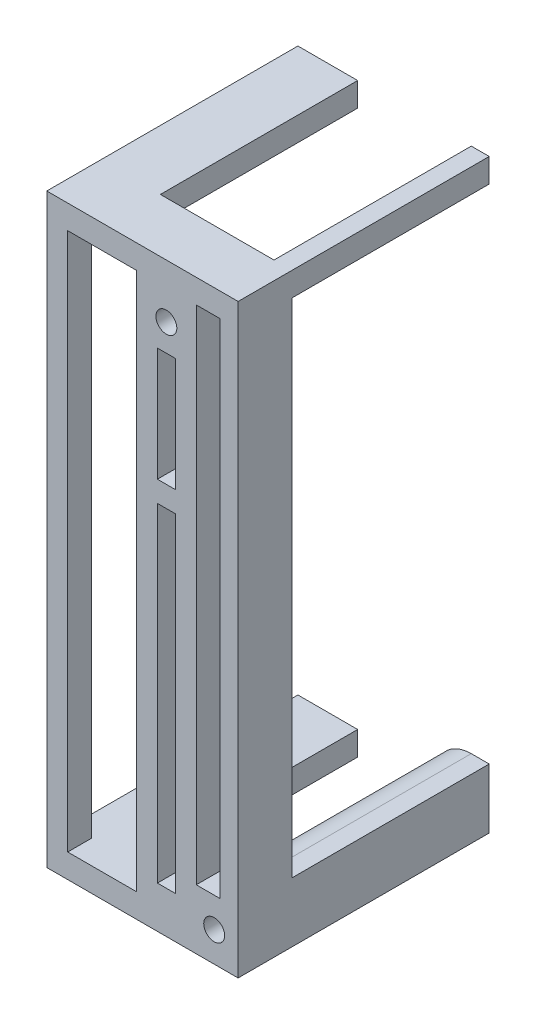
SolidWorks part; units mm, degrees
ref_plane "Front Plane" through (0, 0, 0) normal (0, 0, 1) x (1, 0, 0)
ref_plane "Top Plane" through (0, 0, 0) normal (0, 1, 0) x (1, 0, 0)
ref_plane "Right Plane" through (0, 0, 0) normal (1, 0, 0) x (0, 0, -1)
sketch "Sketch1" plane through (0, 0, 0) normal (0, 0, 1) x (1, 0, 0)
  line L0 (0, 94) -> (32, 94)
  line L1 (0, 0) -> (32, 0)
  line L2 (0, 0) -> (0, 98)
  line L3 (0, 98) -> (32, 98)
  line L4 (32, 0) -> (32, 98)
  line L9 (32, 0) -> (23, 0)
  line L10 (32, 0) -> (32, 10)
  line L11 (32, 10) -> (23, 10)
  line L12 (23, 0) -> (23, 10)
  line L13 (0, 4) -> (32, 4)
  line L14 (29, 0) -> (29, 98)
  line L15 (20, 7) -> (18.5, 7)
  line L20 (32, 0) -> (19, 0)
  line L21 (32, 0) -> (32, 14)
  line L22 (32, 14) -> (19, 14)
  line L23 (19, 0) -> (19, 14)
  line L24 (15, 84) -> (25, 84)
  line L25 (15, 84) -> (15, 94)
  line L26 (15, 94) -> (25, 94)
  line L27 (25, 84) -> (25, 94)
  line L28 (15, 84) -> (25, 94) construction
  line L29 (15, 94) -> (25, 84) construction
  line L30 (11, 94) -> (29, 94)
  line L31 (11, 94) -> (11, 80)
  line L32 (11, 80) -> (29, 80)
  line L33 (29, 94) -> (29, 80)
  line L35 (18.5, 7) -> (21.5, 7)
  line L36 (18.5, 7) -> (18.5, 62)
  line L37 (18.5, 62) -> (21.5, 62)
  line L38 (21.5, 7) -> (21.5, 62)
  line L39 (0, 94) -> (10, 94)
  line L40 (0, 94) -> (0, 98)
  line L41 (0, 98) -> (10, 98)
  line L42 (10, 94) -> (10, 98)
  line L43 (0, 0) -> (10, 0)
  line L44 (0, 0) -> (0, 4)
  line L45 (0, 4) -> (10, 4)
  line L46 (10, 0) -> (10, 4)
  circle A0 centre (20, 89) radius 1.75
  dimension "D9" = 3.5
  dimension "D11" = 10.5
  dimension "D1" = 98
  dimension "D2" = 32
  dimension "D3" = 10
  dimension "D4" = 10
  dimension "D5" = 9
  dimension "D6" = 10
  dimension "D7" = 12
  dimension "D8" = 9
  dimension "D10" = 55
  dimension "D12" = 4
  dimension "D13" = 4
  dimension "D14" = 3
  dimension "D17" = 13
  dimension "D18" = 14
  dimension "D19" = 10
  dimension "D20" = 9
  dimension "D21" = 9
  dimension "D22" = 4
  dimension "D25" = 3
  dimension "D26" = 7
extrude "Boss-Extrude1" add sketch "Sketch1" along normal blind 4 contours L0 L33 L32 L31 L2 L13 L23 L22 L14 L38 L35 L15 L36 L37 | L1 L46 L13 L2 | L46 L1 L23 L13 | L23 L13 L12 L11 L14 L22 | L23 L1 L12 L13 | L4 L22 L14 L11 | L22 L4 L0 L14 | L33 L0 L27 L24 L25 L31 L32 | L42 L0 L14 L3 | L14 L0 L4 L3 | L0 L42 L3 L2 | L24 L27 L0 L25 A0 | L13 L14 L11 L12 | L14 L13 L10 L11 | L14 L9 L4 L13 | L1 L14 L13 L12 region at (5, 96, 0) region at (13.0108, 47.1724, 0) region at (19.5, 96, 0) region at (5, 2, 0) region at (13, 93.772, 0) region at (14.5, 2, 0) region at (20, 93.8586, 0) region at (30.5, 96, 0) region at (19.1414, 5.5, 0) region at (21, 2, 0) region at (30.5, 54, 0) region at (26, 2, 0) region at (26, 7, 0) region at (30.5, 12, 0) region at (30.5, 7, 0) region at (30.5, 2, 0)
extrude "Boss-Extrude3" add sketch "Sketch1<30>" against normal blind 5 contours L1 L46 L13 L2 | L46 L1 L23 L13 | L1 L14 L13 L12 | L23 L1 L12 L13 | L13 L14 L11 L12 | L22 L4 L0 L14 | L14 L0 L4 L3 | L42 L0 L14 L3 | L0 L42 L3 L2 | L4 L22 L14 L11 | L14 L13 L10 L11 | L14 L9 L4 L13 region at (5, 96, 0) region at (19.5, 96, 0) region at (5, 2, 0) region at (14.5, 2, 0) region at (30.5, 96, 0) region at (21, 2, 0) region at (30.5, 54, 0) region at (26, 2, 0) region at (26, 7, 0) region at (30.5, 12, 0) region at (30.5, 7, 0) region at (30.5, 2, 0)
sketch "Sketch1<30>" plane through (0, 0, 0) normal (0, 0, 1) x (1, 0, 0) same geometry as "Sketch1"
extrude "Boss-Extrude4" add sketch "Sketch1<31>" against normal blind 38 contours L1 L46 L13 L2 | L1 L14 L13 L12 | L13 L14 L11 L12 | L14 L13 L10 L11 | L14 L9 L4 L13 | L0 L42 L3 L2 | L14 L0 L4 L3 region at (5, 96, 0) region at (5, 2, 0) region at (30.5, 96, 0) region at (26, 2, 0) region at (26, 7, 0) region at (30.5, 7, 0) region at (30.5, 2, 0)
sketch "Sketch1<31>" plane through (0, 0, 0) normal (0, 0, 1) x (1, 0, 0) same geometry as "Sketch1"
sketch "Sketch3" plane through (0, 0, -38) normal (0, 0, -1) x (-1, 0, 0)
  circle A0 centre (-28, 5) radius 1.75
  dimension "D1" = 3.5
extrude "Cut-Extrude1" cut sketch "Sketch3" against normal through all
fillet "Fillet1" radius 6 1 edges at (23, 10, -19) type face fillet first side face at (23, 4.6667, -14.3333) second side face at (28, 10, -14.3333)
sketch "Sketch4" plane through (0, 0, 0) normal (0, 0, -1) x (-1, 0, 0)
  line L0 (0, 94) -> (-29, 94) construction
  line L1 (-25, 94) -> (-15, 94)
  line L2 (-25, 94) -> (-25, 4)
  line L3 (-25, 4) -> (-15, 4)
  line L4 (-15, 94) -> (-15, 4)
  line L5 (0, 4) -> (-23, 4) construction
  line L6 (-21.5, 7) -> (-21.5, 62) construction
  line L7 (-18.5, 7) -> (-18.5, 62) construction
  line L8 (-18.5, 62) -> (-21.5, 62) construction
  line L9 (-18.5, 65.5) -> (-21.5, 65.5)
  line L10 (-18.5, 65.5) -> (-18.5, 84.5)
  line L11 (-18.5, 84.5) -> (-21.5, 84.5)
  line L12 (-21.5, 65.5) -> (-21.5, 84.5)
  line L13 (0, 4) -> (0, 94) construction
  line L14 (-15, 94) -> (-3.5, 94)
  line L15 (-15, 94) -> (-15, 4)
  line L16 (-15, 4) -> (-3.5, 4)
  line L17 (-3.5, 94) -> (-3.5, 4)
  line L19 (-25, 4) -> (-29, 4)
  line L20 (-25, 4) -> (-25, 94)
  line L21 (-25, 94) -> (-29, 94)
  line L22 (-29, 4) -> (-29, 94)
  line L23 (-25, 4) -> (-29, 4)
  line L24 (-25, 4) -> (-25, 10)
  line L25 (-25, 10) -> (-29, 10)
  line L26 (-29, 4) -> (-29, 10)
  circle A0 centre (-20, 89) radius 1.75 construction
  line M9 (0, 94) -> (-29, 94)
  line M10 (-29, 94) -> (-29, 10)
  arc M11 (-29, 10) -> (-23, 4) centre (-29, 4) cw
  line M12 (-23, 4) -> (0, 4)
  dimension "D3" = 4.5
  dimension "D1" = 3.5
  dimension "D2" = 3.5
  dimension "D4" = 3.5
  dimension "D5" = 3.5
  dimension "D6" = 3.5
  dimension "D7" = 3.5
extrude "Cut-Extrude2" cut sketch "Sketch4" against normal through all contours L17 L4 M9 M12 | L12 L9 L10 L11 | L2 M9 M10 M11 region at (27, 52, 0) region at (9.25, 49, 0) region at (20, 75, 0)
